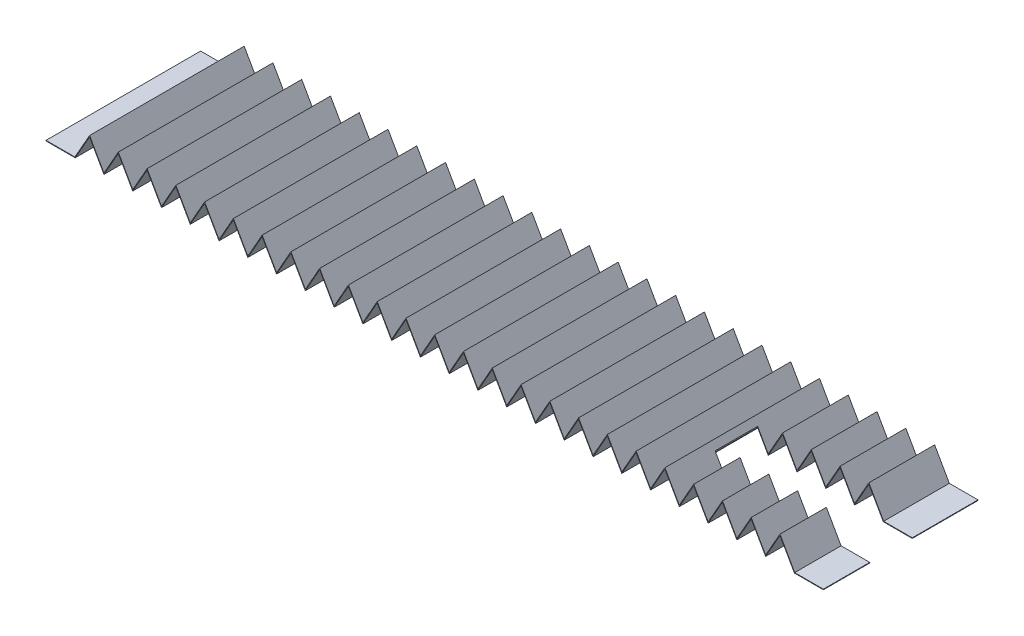
SolidWorks part; units mm, degrees
ref_plane "Front Plane" through (0, 0, 0) normal (0, 0, 1) x (1, 0, 0)
ref_plane "Top Plane" through (0, 0, 0) normal (0, 1, 0) x (1, 0, 0)
ref_plane "Right Plane" through (0, 0, 0) normal (1, 0, 0) x (0, 0, -1)
sketch "Sketch1" plane through (0, 0, 0) normal (0, 0, 1) x (1, 0, 0)
  line L0 (0, 0) -> (7.4417, 13.1389)
  line L1 (7.4417, 13.1389) -> (14.8834, 0)
  line L2 (0, 0) -> (511, 0) construction
  line L3 (14.8834, 0) -> (22.3251, 13.1389)
  line L4 (22.3251, 13.1389) -> (29.7668, 0)
  line L5 (29.7668, 0) -> (37.2085, 13.1389)
  line L6 (37.2085, 13.1389) -> (44.6502, 0)
  line L7 (44.6502, 0) -> (52.0919, 13.1389)
  line L8 (52.0919, 13.1389) -> (59.5336, 0)
  line L9 (59.5336, 0) -> (66.9753, 13.1389)
  line L10 (66.9753, 13.1389) -> (74.417, 0)
  line L11 (74.417, 0) -> (81.8587, 13.1389)
  line L12 (81.8587, 13.1389) -> (89.3004, 0)
  line L13 (89.3004, 0) -> (96.7421, 13.1389)
  line L14 (96.7421, 13.1389) -> (104.1838, 0)
  line L15 (104.1838, 0) -> (111.6255, 13.1389)
  line L16 (111.6255, 13.1389) -> (119.0672, 0)
  line L17 (119.0672, 0) -> (126.5089, 13.1389)
  line L18 (126.5089, 13.1389) -> (133.9506, 0)
  line L19 (0, 0) -> (-15.1, 0)
  line L20 (133.9506, 0) -> (141.3923, 13.1389)
  line L21 (141.3923, 13.1389) -> (148.834, 0)
  line L22 (148.834, 0) -> (156.2757, 13.1389)
  line L23 (156.2757, 13.1389) -> (163.7174, 0)
  line L24 (163.7174, 0) -> (171.1591, 13.1389)
  line L25 (171.1591, 13.1389) -> (178.6008, 0)
  line L26 (178.6008, 0) -> (186.0425, 13.1389)
  line L27 (186.0425, 13.1389) -> (193.4842, 0)
  line L28 (193.4842, 0) -> (200.9259, 13.1389)
  line L29 (200.9259, 13.1389) -> (208.3676, 0)
  line L30 (208.3676, 0) -> (215.8093, 13.1389)
  line L31 (215.8093, 13.1389) -> (223.251, 0)
  line L32 (223.251, 0) -> (230.6927, 13.1389)
  line L33 (230.6927, 13.1389) -> (238.1344, 0)
  line L34 (238.1344, 0) -> (245.5761, 13.1389)
  line L35 (245.5761, 13.1389) -> (253.0178, 0)
  line L36 (253.0178, 0) -> (260.4595, 13.1389)
  line L37 (260.4595, 13.1389) -> (267.9012, 0)
  line L38 (289.085, -119) -> (289.085, 132.963) construction
  line L39 (267.9012, 0) -> (275.3429, 13.1389)
  line L40 (275.3429, 13.1389) -> (282.7846, 0)
  line L41 (282.7846, 0) -> (290.2263, 13.1389)
  line L42 (290.2263, 13.1389) -> (297.668, 0)
  line L43 (297.668, 0) -> (305.1097, 13.1389)
  line L44 (305.1097, 13.1389) -> (312.5514, 0)
  line L45 (312.5514, 0) -> (319.9931, 13.1389)
  line L46 (319.9931, 13.1389) -> (327.4348, 0)
  line L47 (327.4348, 0) -> (334.8765, 13.1389)
  line L48 (334.8765, 13.1389) -> (342.3182, 0)
  line L49 (342.3182, 0) -> (349.7599, 13.1389)
  line L51 (349.7599, 13.1389) -> (357.2016, 0)
  line L52 (357.2016, 0) -> (364.6433, 13.1389)
  line L53 (364.6433, 13.1389) -> (372.085, 0)
  line L54 (372.085, 0) -> (387.085, 0)
  dimension "D1" = 511
  dimension "D2" = 15.1
  dimension "D3" = 15
  dimension "D4" = 14.8834
  dimension "D6" = 98
  dimension "D5" = 25
extrude "Extrude-Thin1" add sketch "Sketch1" along normal mid plane 80 thin thin type one direction reverse wall 0.3
sketch "Sketch2" plane through (0, 0, 0) normal (0, 1, 0) x (1, 0, 0)
  line L1 (307.085, -16) -> (387.085, -16)
  line L2 (307.085, -16) -> (307.085, 6)
  line L3 (307.085, 6) -> (387.085, 6)
  line L4 (387.085, -16) -> (387.085, 6)
  line L5 (307.085, -16) -> (387.085, 6) construction
  line L6 (307.085, 6) -> (387.085, -16) construction
  line L8 (387.085, -40) -> (387.085, 40) construction
  point P0 (347.085, -5)
  dimension "D1" = 80
  dimension "D2" = 22
  dimension "D3" = 5
extrude "Cut-Extrude4" cut sketch "Sketch2" against normal through all and the other way through all contours L1 L4 L3 L2 region at (347.085, 0, 5)
